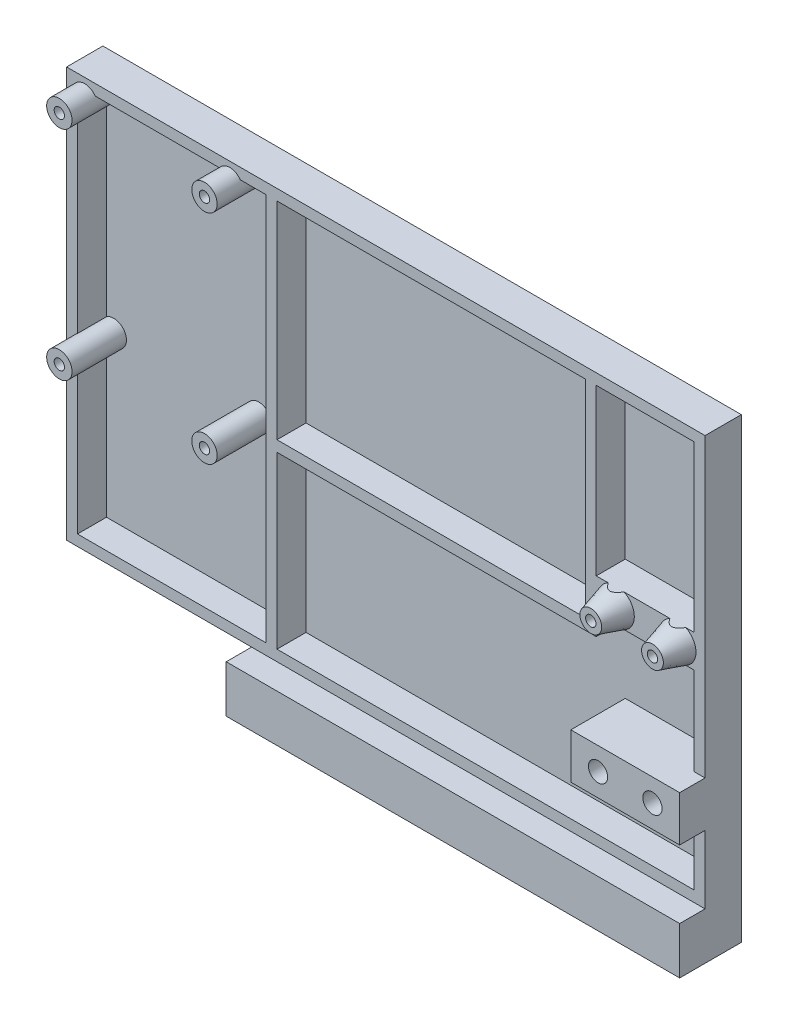
SolidWorks part; units mm, degrees
material "ABS"
ref_plane "Front Plane" through (0, 0, 0) normal (0, 0, 1) x (1, 0, 0)
ref_plane "Top Plane" through (0, 0, 0) normal (0, 1, 0) x (1, 0, 0)
ref_plane "Right Plane" through (0, 0, 0) normal (1, 0, 0) x (0, 0, -1)
sketch "Sketch1" plane through (0, 0, 0) normal (0, 0, 1) x (1, 0, 0)
  line L0 (-45.5, -31.5) -> (-45.5, 31.5) construction
  line L1 (-42.5, -28.5) -> (42.5, -28.5)
  line L2 (-42.5, -28.5) -> (-42.5, 28.5)
  line L3 (-42.5, 28.5) -> (42.5, 28.5)
  line L4 (42.5, -28.5) -> (42.5, 28.5)
  line L5 (-42.5, -28.5) -> (42.5, 28.5) construction
  line L6 (-42.5, 28.5) -> (42.5, -28.5) construction
  line L7 (-45.5, -81.5) -> (75.5, -81.5) construction
  line L8 (-45.5, -81.5) -> (-45.5, -31.5) construction
  line L9 (-45.5, -31.5) -> (75.5, -31.5) construction
  line L10 (75.5, -81.5) -> (75.5, -31.5) construction
  line L11 (-45.5, -81.5) -> (75.5, -31.5) construction
  line L12 (-45.5, -31.5) -> (75.5, -81.5) construction
  line L17 (-45.5, 31.5) -> (45.5, 31.5) construction
  line L18 (45.5, -31.5) -> (45.5, 31.5) construction
  line L19 (-45.5, -31.5) -> (45.5, -31.5) construction
  line L21 (45.5, 31.5) -> (75.5, 31.5) construction
  line L22 (45.5, 31.5) -> (45.5, -31.5) construction
  line L23 (45.5, -31.5) -> (75.5, -31.5) construction
  line L24 (75.5, 31.5) -> (75.5, -31.5) construction
  line L25 (-45.5, 31.5) -> (75.5, 31.5)
  line L26 (-45.5, 31.5) -> (-45.5, -81.5)
  line L27 (-45.5, -81.5) -> (75.5, -81.5)
  line L28 (75.5, 31.5) -> (75.5, -81.5)
  circle A0 centre (68, -56.5) radius 2.65
  circle A1 centre (53, -56.5) radius 2.65
  circle A2 centre (51, -21.5) radius 1.425
  circle A3 centre (68, -21.5) radius 1.425
  point P0 (0, 0)
  point P6 (15, -56.5)
  dimension "D4" = 15
  dimension "D5" = 7.5
  dimension "D6" = 5.3
  dimension "D10" = 2.85
  dimension "D1" = 85
  dimension "D2" = 57
  dimension "D3" = 50
  dimension "D7" = 30
  dimension "D8" = 10
  dimension "D11" = 17
  dimension "D9" = 3
extrude "Boss-Extrude1" add sketch "Sketch1" along normal blind 10
sketch "Sketch2" plane through (0, 0, 0) normal (0, 0, -1) x (-1, 0, 0)
  line L1 (-42.5, 28.5) -> (42.5, 28.5)
  line L2 (-42.5, 28.5) -> (-42.5, -28.5)
  line L3 (-42.5, -28.5) -> (42.5, -28.5)
  line L4 (42.5, 28.5) -> (42.5, -28.5)
extrude "Boss-Extrude2" add sketch "Sketch2" against normal blind 2
sketch "Sketch4" plane through (0, 0, 10) normal (0, 0, 1) x (1, 0, 0)
  line L0 (-42.5, 28.5) -> (-45.5, 31.5) construction
  line L1 (-45.5, 31.5) -> (45.5, 31.5)
  line L2 (-45.5, 31.5) -> (-45.5, -31.5)
  line L3 (-45.5, -31.5) -> (45.5, -31.5)
  line L4 (45.5, 31.5) -> (45.5, -31.5)
  line L5 (42.5, -28.5) -> (45.5, -31.5) construction
  line L6 (-45.5, -31.5) -> (-45.5, -81.5)
  line L7 (-45.5, -81.5) -> (75.5, -81.5)
  line L8 (75.5, -81.5) -> (75.5, 31.5)
  line L9 (75.5, 31.5) -> (45.5, 31.5)
  line L10 (45.5, -31.5) -> (45.5, 31.5)
  line L11 (-45.5, -31.5) -> (45.5, -31.5)
  line L12 (-45.5, -81.5) -> (-45.5, -31.5)
  line L13 (53, -56.5) -> (68, -56.5) construction
  line L14 (-42.5, -28.5) -> (-42.5, -78.5)
  line L15 (45.5, -62.75) -> (75.5, -62.75)
  line L16 (45.5, -62.75) -> (45.5, -50.25)
  line L17 (45.5, -50.25) -> (75.5, -50.25)
  line L18 (75.5, -62.75) -> (75.5, -50.25)
  line L19 (45.5, -62.75) -> (75.5, -50.25) construction
  line L20 (45.5, -50.25) -> (75.5, -62.75) construction
  line L21 (-42.5, -78.5) -> (72.5, -78.5)
  line L22 (72.5, -78.5) -> (72.5, -62.75)
  line L23 (45.5, 28.5) -> (72.5, 28.5)
  line L24 (72.5, 28.5) -> (72.5, -21.5)
  line L25 (72.5, -21.5) -> (72.5, -50.25)
  line L26 (-42.5, -78.5) -> (-45.5, -81.5) construction
  line L27 (72.5, -78.5) -> (75.5, -81.5) construction
  line L28 (72.5, 28.5) -> (75.5, 31.5) construction
  line L29 (51, -21.5) -> (68, -21.5) construction
  line L31 (73.5, -26) -> (45.5, -26)
  line L32 (73.5, -26) -> (73.5, -17)
  line L33 (73.5, -17) -> (45.5, -17)
  line L34 (45.5, -26) -> (45.5, -17)
  line L35 (73.5, -26) -> (45.5, -17) construction
  line L36 (73.5, -17) -> (45.5, -26) construction
  circle A2 centre (53, -56.5) radius 2.65
  circle A3 centre (68, -56.5) radius 2.65
  circle A6 centre (68, -56.5) radius 2.65 construction
  point P21 (60.5, -56.5)
  point P29 (59.5, -21.5)
  dimension "D2" = 9
  dimension "D1" = 12.5
extrude "Cut-Extrude1" cut sketch "Sketch4" against normal up to surface (8 mm away) contours L33 L24 L23 L10 | L25 L31 L4 L11 L14 L21 L22 L15 L16 L17 region at (59, 5.75, 10) region at (13.4057, -54.1556, 10) up to face at (0, 0, 2)
sketch "Sketch5" plane through (0, 0, 0) normal (0, 0, -1) x (-1, 0, 0)
  line L1 (-64.25, -25.25) -> (-71.75, -25.25) construction
  line L2 (-64.25, -25.25) -> (-64.25, -17.75) construction
  line L3 (-64.25, -17.75) -> (-71.75, -17.75) construction
  line L4 (-71.75, -25.25) -> (-71.75, -17.75) construction
  line L5 (-64.25, -25.25) -> (-71.75, -17.75) construction
  line L6 (-64.25, -17.75) -> (-71.75, -25.25) construction
  line L7 (-47.25, -25.25) -> (-54.75, -25.25) construction
  line L8 (-47.25, -25.25) -> (-47.25, -17.75) construction
  line L9 (-47.25, -17.75) -> (-54.75, -17.75) construction
  line L10 (-54.75, -25.25) -> (-54.75, -17.75) construction
  line L11 (-47.25, -25.25) -> (-54.75, -17.75) construction
  line L12 (-47.25, -17.75) -> (-54.75, -25.25) construction
  line L13 (-73.25, -61.75) -> (-62.75, -61.75)
  line L14 (-73.25, -61.75) -> (-73.25, -51.25)
  line L15 (-73.25, -51.25) -> (-62.75, -51.25)
  line L16 (-62.75, -61.75) -> (-62.75, -51.25)
  line L17 (-73.25, -61.75) -> (-62.75, -51.25) construction
  line L18 (-73.25, -51.25) -> (-62.75, -61.75) construction
  line L19 (-47.75, -61.75) -> (-58.25, -61.75)
  line L20 (-47.75, -61.75) -> (-47.75, -51.25)
  line L21 (-47.75, -51.25) -> (-58.25, -51.25)
  line L22 (-58.25, -61.75) -> (-58.25, -51.25)
  line L23 (-47.75, -61.75) -> (-58.25, -51.25) construction
  line L24 (-47.75, -51.25) -> (-58.25, -61.75) construction
  point P0 (-68, -21.5)
  point P6 (-51, -21.5)
  point P12 (-68, -56.5)
  point P18 (-53, -56.5)
  dimension "D1" = 7.5
  dimension "D2" = 10.5
extrude "Cut-Extrude2" cut sketch "Sketch5" against normal blind 7
sketch "Sketch7" plane through (0, 0, 10) normal (0, 0, 1) x (1, 0, 0)
  line L0 (75.5, -81.5) -> (75.5, 31.5) construction
  line L1 (45.5, -50.25) -> (75.5, -50.25)
  line L2 (45.5, -50.25) -> (45.5, -62.75)
  line L3 (45.5, -62.75) -> (75.5, -62.75)
  line L4 (75.5, -50.25) -> (75.5, -62.75)
  line L5 (45.5, -62.75) -> (72.5, -62.75) construction
  circle A0 centre (51, -21.5) radius 1.425
  circle A1 centre (51, -21.5) radius 3
  circle A2 centre (68, -21.5) radius 3
  circle A3 centre (68, -21.5) radius 1.425
  circle A4 centre (53, -56.5) radius 2.65
  circle A5 centre (68, -56.5) radius 2.65
  circle A6 centre (53, -56.5) radius 2.65 construction
  circle A7 centre (51, -21.5) radius 1.425 construction
  dimension "D1" = 6
extrude "Boss-Extrude4" add sketch "Sketch7" along normal blind 7
chamfer "Chamfer2" distance 2 distance2 7 2 edges at (65, -21.5, 10) (48, -21.5, 10) first distance on face at (65, -21.5, 10)
sketch "Sketch9" plane through (0, 0, 0) normal (0, 0, -1) x (-1, 0, 0)
  line L0 (45.5, -81.5) -> (-75.5, -81.5) construction
  line L1 (45.5, 31.5) -> (100.5, 31.5)
  line L2 (45.5, 31.5) -> (45.5, -81.5)
  line L3 (45.5, -81.5) -> (100.5, -81.5)
  line L4 (100.5, 31.5) -> (100.5, -81.5)
  dimension "D1" = 55
extrude "Boss-Extrude5" add sketch "Sketch9" against normal up to surface (17 mm away) up to face at (54, -21.5, 17)
sketch "Sketch10" plane through (0, 0, 17) normal (0, 0, 1) x (1, 0, 0)
  line L1 (-95.5, -33.5) -> (-55.5, -33.5) construction
  line L2 (-95.5, -33.5) -> (-95.5, 26.5) construction
  line L3 (-95.5, 26.5) -> (-55.5, 26.5) construction
  line L4 (-55.5, -33.5) -> (-55.5, 26.5) construction
  line L5 (-95.5, -33.5) -> (-55.5, 26.5) construction
  line L6 (-95.5, 26.5) -> (-55.5, -33.5) construction
  line L8 (-50.5, -38.5) -> (-100.5, -38.5) construction
  line L9 (-50.5, -38.5) -> (-50.5, 31.5) construction
  line L10 (-50.5, 31.5) -> (-100.5, 31.5) construction
  line L11 (-100.5, -38.5) -> (-100.5, 31.5) construction
  line L12 (-50.5, -38.5) -> (-100.5, 31.5) construction
  line L13 (-50.5, 31.5) -> (-100.5, -38.5) construction
  circle A0 centre (-95.5, 26.5) radius 1.425
  circle A1 centre (-55.5, 26.5) radius 1.425
  circle A2 centre (-95.5, -33.5) radius 1.425
  circle A3 centre (-55.5, -33.5) radius 1.425
  point P0 (-75.5, -3.5)
  point P9 (-75.5, -3.5)
  dimension "D3" = 2.85
  dimension "D1" = 60
  dimension "D2" = 40
  dimension "D4" = 50
  dimension "D5" = 70
extrude "Cut-Extrude3" cut sketch "Sketch10" against normal through all
sketch "Sketch11" plane through (0, 0, 17) normal (0, 0, 1) x (1, 0, 0)
  line L0 (-48.5, 28.5) -> (-45.5, 28.5)
  line L1 (-45.5, 31.5) -> (-45.5, -81.5) construction
  line L2 (-48.5, -78.5) -> (-45.5, -78.5)
  line L3 (-45.5, 31.5) -> (-45.5, -81.5) construction
  line L4 (-45.5, -78.5) -> (-45.5, 28.5)
  line L8 (-48.5, -78.5) -> (-48.5, 28.5)
  line L9 (-48.5, 28.5) -> (-97.5, 28.5)
  line L10 (-97.5, 28.5) -> (-97.5, -78.5)
  line L11 (-97.5, -78.5) -> (-48.5, -78.5)
  line L12 (-48.5, -78.5) -> (-48.5, 28.5) construction
  line L13 (-48.5, 28.5) -> (-97.5, 28.5)
  line L14 (-97.5, 28.5) -> (-97.5, -78.5)
  line L15 (-97.5, -78.5) -> (-48.5, -78.5)
  circle A0 centre (-95.5, 26.5) radius 3.5
  circle A1 centre (-55.5, 26.5) radius 3.5
  circle A2 centre (-95.5, -33.5) radius 3.5
  circle A3 centre (-55.5, -33.5) radius 3.5
  line M10 (-45.5, -81.5) -> (-45.5, 31.5)
  dimension "D1" = 7
  dimension "D2" = 3
extrude "Cut-Extrude4" cut sketch "Sketch11" against normal up to surface (15 mm away) contours L15 L12 L13 A1 A0 L14 A2 A3 | L12 L2 L0 M10 region at (-47, -25, 17) region at (-72.988, -25.473, 17) up to face at (0, 0, 2)
sketch "Sketch12" plane through (0, 0, 17) normal (0, 0, 1) x (1, 0, 0)
  line L5 (-100.5, -81.5) -> (-45.5, -81.5)
  line L6 (-100.5, -81.5) -> (-100.5, 31.5)
  line L7 (-100.5, 31.5) -> (-45.5, 31.5)
  line L8 (-45.5, -81.5) -> (-45.5, 31.5)
  circle A0 centre (-95.5, 26.5) radius 3.5
  circle A1 centre (-55.5, 26.5) radius 3.5
  circle A2 centre (-95.5, -33.5) radius 3.5
  circle A3 centre (-55.5, -33.5) radius 3.5
  arc A4 (-97.5, -36.3723) -> (-97.5, -30.6277) centre (-95.5, -33.5) ccw construction
extrude "Cut-Extrude5" cut sketch "Sketch12" against normal up to surface (7 mm away) up to face at (37.0833, -29.625, 10)
sketch "Sketch13" plane through (0, -81.5, 0) normal (0, -1, 0) x (1, 0, 0)
  line L0 (71.5, 4) -> (-45.5, 4) construction
  line L1 (-49.5, 0) -> (75.5, 0)
  line L2 (-49.5, 0) -> (-49.5, 17)
  line L3 (-49.5, 17) -> (75.5, 17)
  line L4 (75.5, 0) -> (75.5, 17)
  line L5 (42.25, 4) -> (-16.25, 4) construction
  line L6 (-100.5, 0) -> (75.5, 0) construction
  line L7 (13, 4) -> (-16.25, 4) construction
  line L8 (-16.25, 4) -> (-45.5, 4) construction
  circle A0 centre (71.5, 4) radius 4 construction
  circle A1 centre (-45.5, 4) radius 4 construction
  circle A2 centre (-16.25, 4) radius 1.9
  circle A3 centre (42.25, 4) radius 1.9
  circle A4 centre (71.5, 4) radius 1.9
  circle A5 centre (-45.5, 4) radius 1.9
  point P9 (13, 4)
  point P12 (13, 4)
  dimension "D1" = 8
  dimension "D3" = 3.8
  dimension "D2" = 125
extrude "Boss-Extrude6" add sketch "Sketch13" along normal blind 13
